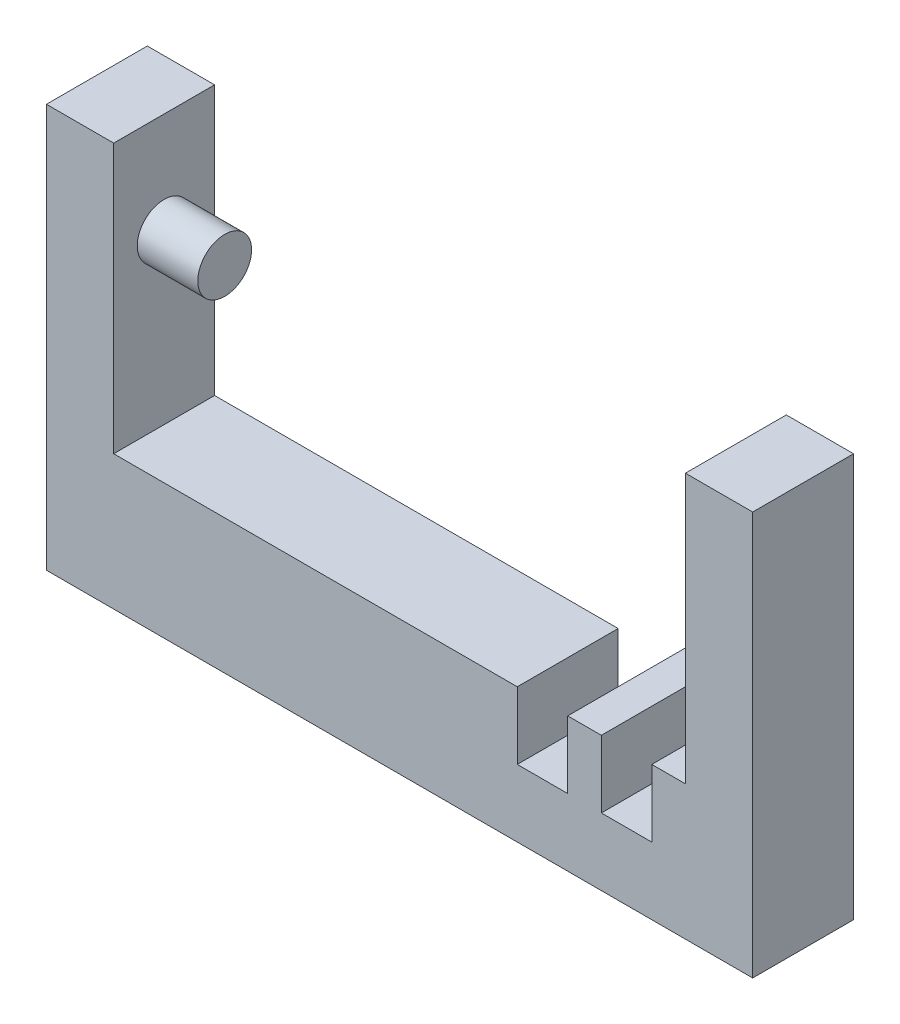
SolidWorks part; units mm, degrees
ref_plane "Front Plane" through (0, 0, 0) normal (0, 0, 1) x (1, 0, 0)
ref_plane "Top Plane" through (0, 0, 0) normal (0, 1, 0) x (1, 0, 0)
ref_plane "Right Plane" through (0, 0, 0) normal (1, 0, 0) x (0, 0, -1)
sketch "Sketch1" plane through (0, 0, 0) normal (0, 1, 0) x (1, 0, 0)
  line L0 (32.5, 7.5) -> (32.5, -7.5)
  line L1 (-40, 7.5) -> (40, 7.5)
  line L2 (-40, 7.5) -> (-40, -7.5)
  line L3 (-40, -7.5) -> (40, -7.5)
  line L4 (40, 7.5) -> (40, -7.5)
  line L5 (27.5, 7.5) -> (27.5, -7.5)
  line L6 (20, 7.5) -> (20, -7.5)
  line L11 (40, 7.5) -> (45, 7.5)
  line L12 (45, 7.5) -> (45, -7.5)
  line L13 (45, -7.5) -> (40, -7.5)
  line L14 (45, 7.5) -> (55, 7.5)
  line L15 (55, 7.5) -> (55, -7.5)
  line L16 (55, -7.5) -> (45, -7.5)
  line L17 (-40, 7.5) -> (-50, 7.5)
  line L18 (-50, 7.5) -> (-50, -7.5)
  line L19 (-50, -7.5) -> (-40, -7.5)
  point P4 (0, -7.5)
  point P8 (-40, 0)
  dimension "D1" = 80
  dimension "D2" = 15
  dimension "D3" = 7.5
  dimension "D4" = 5
  dimension "D5" = 10
  dimension "D6" = 7.5
  dimension "D7" = 5
  dimension "D8" = 10
extrude "Boss-Extrude2" add sketch "Sketch1<3>" along normal blind 10 separate body contours L4 L1 L0 L3 | L1 L6 L3 L5 region at (36.25, 0, 0) region at (23.75, 0, 0)
sketch "Sketch1<3>" plane through (0, 0, 0) normal (0, 1, 0) x (1, 0, 0) same geometry as "Sketch1"
extrude "Boss-Extrude3" add sketch "Sketch1" along normal blind 20 contours L1 L5 L3 L0 | L6 L1 L2 L3 | L13 L12 L11 L4 region at (30, 0, 0) region at (42.5, 0, 0) region at (-10, 0, 0)
sketch "Sketch2" plane through (0, 0, -7.5) normal (0, 0, -1) x (-1, 0, 0)
  line L0 (-27.5, 20) -> (-27.5, 10) construction
  line L1 (-32.5, 20) -> (-27.5, 20)
  line L2 (-32.5, 20) -> (-32.5, 15)
  line L3 (-32.5, 15) -> (-27.5, 15)
  line L4 (-27.5, 20) -> (-27.5, 15)
  dimension "D1" = 5
extrude "Boss-Extrude5" add sketch "Sketch2" along normal blind 5
extrude "Boss-Extrude6" add sketch "Sketch1<9>" along normal blind 60 contours L16 L15 L14 L12 | L18 L19 L2 L17 region at (50, 0, 0) region at (-45, 0, 0)
sketch "Sketch1<9>" plane through (0, 0, 0) normal (0, 1, 0) x (1, 0, 0) same geometry as "Sketch1"
sketch "Sketch4" plane through (-40, 0, 0) normal (1, 0, 0) x (0, 0, -1)
  line L0 (7.5, 60) -> (-7.5, 60) construction
  circle A0 centre (0, 45) radius 4
  dimension "D2" = 8
  dimension "D1" = 15
extrude "Boss-Extrude7" add sketch "Sketch4" along normal blind 9
sketch "Sketch5" plane through (32.5, 0, 0) normal (1, 0, 0) x (0, 0, -1)
  line L0 (12.5, 15) -> (7.5, 15) construction
  line L1 (12.5, 20) -> (12.5, 15) construction
  circle A0 centre (10, 17.5) radius 1.5
  point P4 (10, 15)
  point P7 (12.5, 17.5)
  dimension "D1" = 3
extrude "Cut-Extrude1" cut sketch "Sketch5" against normal blind 5
